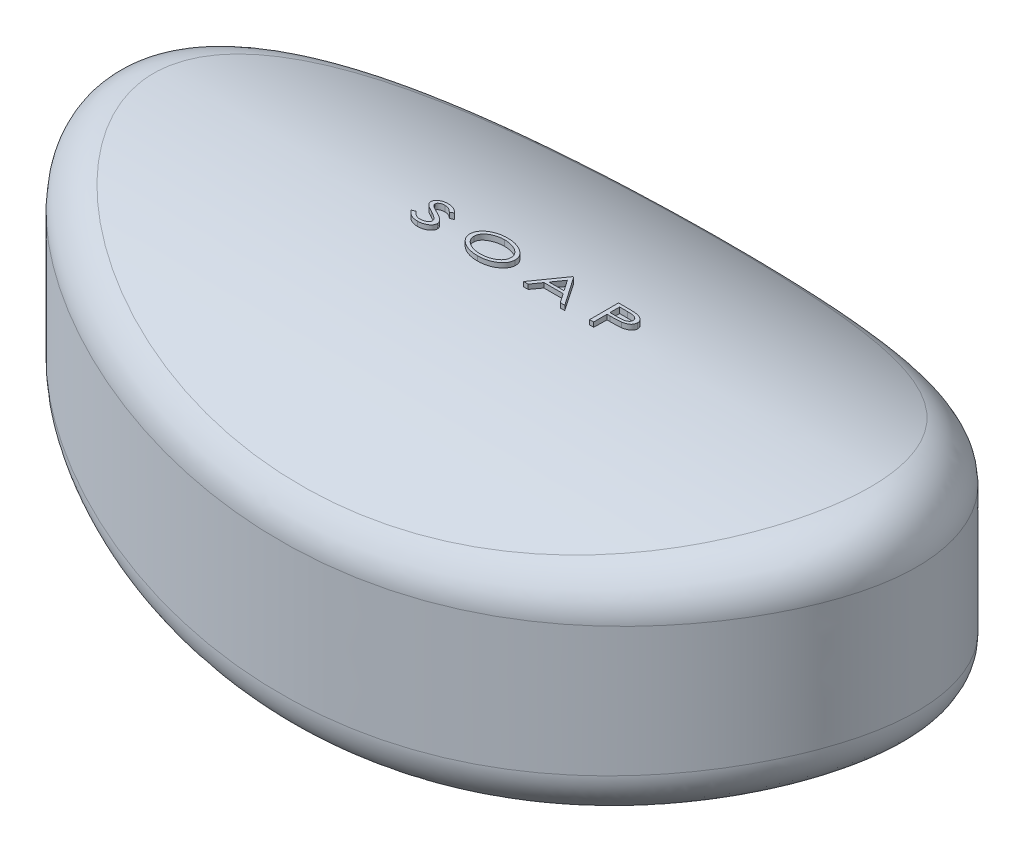
SolidWorks part; units mm, degrees
ref_plane "Front Plane" through (0, 0, 0) normal (0, 0, 1) x (1, 0, 0)
ref_plane "Top Plane" through (0, 0, 0) normal (0, 1, 0) x (1, 0, 0)
ref_plane "Right Plane" through (0, 0, 0) normal (1, 0, 0) x (0, 0, -1)
sketch "Sketch2" plane through (0, 0, 0) normal (0, 1, 0) x (1, 0, 0)
  ellipse E0 centre (0, 0) end of major axis (44.45, 0) minor radius 25.4
  point P9 (44.6795, -8.0586)
  dimension "D1" = 25.4
  dimension "D2" = 44.45
extrude "Boss-Extrude1" add sketch "Sketch2" along normal blind 31.75
sketch "Sketch3" plane through (0, 0, 0) normal (0, 0, 1) x (1, 0, 0)
  line L0 (-44.45, 31.75) -> (-44.45, 0) construction
  line L1 (-44.45, 0) -> (44.45, 0) construction
  line L2 (44.45, 0) -> (44.45, 31.75) construction
  line L3 (-44.45, 9.525) -> (44.45, 9.525) construction
  line L4 (-44.45, 9.525) -> (-62.2871, 9.525)
  line L5 (-62.2871, 9.525) -> (-62.2871, -26.9277)
  line L6 (-62.2871, -26.9277) -> (57.7436, -27.6715)
  line L7 (57.7436, -27.6715) -> (57.7436, 9.525)
  line L8 (57.7436, 9.525) -> (44.45, 9.525)
  spline S0 degree 2 poles (-44.45, 9.525) (0, -9.525) (44.45, 9.525) knots 0 0 0 1 1 1
  dimension "D1" = 9.525
sketch "Sketch4" plane through (0, 0, 0) normal (1, 0, 0) x (0, 0, -1)
  line L0 (-25.4, 31.75) -> (-25.4, 0) construction
  line L1 (25.4, 31.75) -> (-25.4, 31.75) construction
  line L2 (25.4, 0) -> (25.4, 31.75) construction
  line L3 (-25.4, 22.225) -> (25.4, 22.225) construction
  line L4 (-25.4, 22.225) -> (-31.2536, 22.225)
  line L5 (-31.2536, 22.225) -> (-29.6321, 34.9945)
  line L6 (-29.6321, 34.9945) -> (31.1163, 35.4578)
  line L7 (31.1163, 35.4578) -> (30.7109, 22.225)
  line L8 (30.7109, 22.225) -> (25.4, 22.225)
  spline S0 degree 2 poles (-25.4, 22.225) (0, 41.275) (25.4, 22.225) knots 0 0 0 1 1 1
  dimension "D1" = 9.525
extrude "Cut-Extrude2" cut sketch "Sketch4" against normal mid plane 152.4 contours L5 L6 L7 L8 S0 L4
sketch "Sketch8" plane through (0, 0, 0) normal (0, 1, 0) x (1, 0, 0)
  line L0 (-44.45, 0) -> (44.45, 0) construction
  line L1 (-44.45, 0) -> (44.45, 0) construction
  ellipse E0 centre (0, 0) end of major axis (44.45, 0) minor radius 25.4 construction
  text T0 "SOAP" font "Century Gothic" height 3.175
extrude "Boss-Extrude3" add sketch "Sketch8" along normal blind 32.258
extrude "Cut-Extrude3" cut sketch "Sketch3" against normal mid plane 87.884 contours L4 L5 L6 L7 L8 S0
fillet "Fillet2" radius 5.08 2 edges at (-44.4325, 9.5175, 0.7117) (44.4372, 31.7445, 0.6092)
